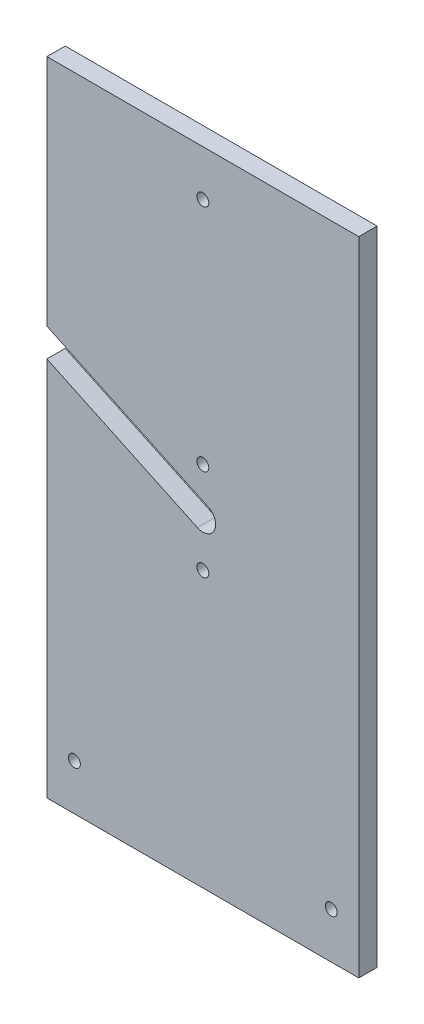
SolidWorks part; units mm, degrees
ref_plane "Ebene vorne" through (0, 0, 0) normal (0, 0, 1) x (1, 0, 0)
ref_plane "Ebene oben" through (0, 0, 0) normal (0, 1, 0) x (1, 0, 0)
ref_plane "Ebene rechts" through (0, 0, 0) normal (1, 0, 0) x (0, 0, -1)
sketch "Skizze1" plane through (0, 0, 0) normal (0, 0, 1) x (1, 0, 0)
  line L11 (0, 0) -> (-85, 40) construction
  line L27 (85, 175) -> (-85, 175)
  line L28 (85, 175) -> (85, -175)
  line L29 (85, -175) -> (-85, -175)
  line L30 (-85, 175) -> (-85, 47.7364)
  line L31 (85, 175) -> (-85, -175) construction
  line L32 (85, -175) -> (-85, 175) construction
  line L33 (-2.9806, -6.3337) -> (-85, 32.2636)
  line L36 (2.9806, 6.3337) -> (-85, 47.7364)
  line L37 (-85, 32.2636) -> (-85, -175)
  arc A6 (-2.9806, -6.3337) -> (2.9806, 6.3337) centre (0, 0) ccw
  point P0 (0, 0)
  point P7 (-43.367, 12.2952)
  point P10 (50, 0)
  point P11 (-70, -150)
  point P12 (50, 240)
  point P16 (-25, -43.3013)
  point P17 (182.8461, -163.3013)
  point P18 (-25, 43.3013)
  point P20 (-232.8461, -76.6987)
  point P21 (-50, 0)
  point P22 (-50, 240)
  point P23 (25, 43.3013)
  point P24 (232.8461, -76.6987)
  point P25 (25, -43.3013)
  point P26 (-182.8461, -163.3013)
  point P29 (70, -150)
  point P30 (0, 150)
  point P32 (0, 175)
  dimension "D3" = 350
  dimension "D8" = 15
  dimension "D1" = 7
  dimension "D2" = 170
  dimension "D4" = 25
  dimension "D5" = 25
  dimension "D6" = 25
  dimension "D7" = 40
  dimension "D9" = 15
  dimension "D10" = 7
  dimension "D11" = 7
extrude "Aufsatz-Linear austragen1" add sketch "Skizze1" along normal blind 10 contours L30 L36 A6 L33 L37 L29 L28 L27
hole_wizard "Ø6.5 (6.5) Durchmesser Bohrung5" positions "Skizze19" profile "Skizze18" hole size "Ø6.5" standard "ISO" end condition through all
sketch "Skizze19" plane through (0, 0, 10) normal (0, 0, 1) x (1, 0, 0)
  point P0 (0, 150)
  point P3 (-70, -150)
  point P6 (70, -150)
  point P9 (0, 25)
  point P11 (0, -25)
  dimension "D1" = 25
  dimension "D2" = 25
sketch "Skizze18" plane through (0, 150, 10) normal (1, 0, 0) x (0, -1, 0)
  line L0 (0, 0) -> (0, 10)
  line L1 (0, 10) -> (3.25, 10)
  line L2 (3.25, 10) -> (3.25, 0)
  line L5 (3.25, 0) -> (0, 0)
  line L11 (0, -6.35) -> (0, 107.95) construction
  dimension "Bohrerdurchmesser" = 6.5
  dimension "Bohrungstiefe" = 10
